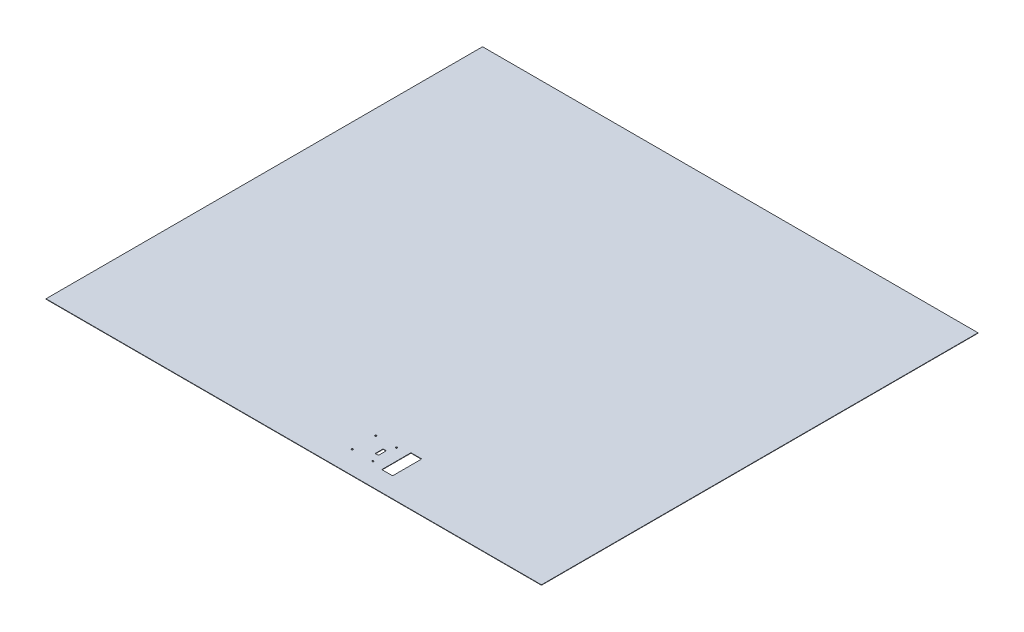
SolidWorks part; units mm, degrees
ref_plane "Front Plane" through (0, 0, 0) normal (0, 0, 1) x (1, 0, 0)
ref_plane "Top Plane" through (0, 0, 0) normal (0, 1, 0) x (1, 0, 0)
ref_plane "Right Plane" through (0, 0, 0) normal (1, 0, 0) x (0, 0, -1)
sketch "Sketch1" plane through (0, 0, 0) normal (0, 1, 0) x (1, 0, 0)
  line L1 (612.6065, -310.951) -> (-627.8935, -310.951)
  line L2 (612.6065, -310.951) -> (612.6065, 782.049)
  line L3 (612.6065, 782.049) -> (-627.8935, 782.049)
  line L4 (-627.8935, -310.951) -> (-627.8935, 782.049)
  dimension "D1" = 1093
  dimension "D2" = 1240.5
extrude "Boss-Extrude1" add sketch "Sketch1" along normal blind 1
sketch "Sketch2" plane through (0, 1, 0) normal (0, 1, 0) x (1, 0, 0)
  line L0 (-627.8935, -310.951) -> (612.6065, -310.951) construction
  line L1 (162.8565, -187.951) -> (189.8565, -187.951)
  line L2 (162.8565, -187.951) -> (162.8565, -260.951)
  line L3 (162.8565, -260.951) -> (189.8565, -260.951)
  line L4 (189.8565, -187.951) -> (189.8565, -260.951)
  line L5 (612.6065, -310.951) -> (612.6065, 782.049) construction
  line L6 (-627.8935, 782.049) -> (-627.8935, -310.951) construction
  point P6 (176.3565, -260.951)
  point P9 (189.8565, -224.451)
  dimension "D1" = 27
  dimension "D2" = 73
  dimension "D3" = 50
  dimension "D4" = 422.75
  dimension "D5" = 790.75
extrude "Cut-Extrude1" cut sketch "Sketch2" against normal blind 1
sketch "Sketch3" plane through (0, 1, 0) normal (0, 1, 0) x (1, 0, 0)
  line L0 (189.8565, -187.951) -> (162.8565, -187.951) construction
  line L1 (162.8565, -260.951) -> (189.8565, -260.951) construction
  line L2 (162.8565, -187.951) -> (162.8565, -260.951) construction
  circle A0 centre (133.6565, -194.951) radius 2
  circle A1 centre (133.6565, -253.951) radius 2
  circle A2 centre (81.9765, -194.951) radius 2
  circle A3 centre (81.9765, -253.951) radius 2
  dimension "D1" = 4
  dimension "D2" = 4
  dimension "D3" = 4
  dimension "D4" = 4
  dimension "D5" = 7
  dimension "D6" = 7
  dimension "D7" = 29.2
  dimension "D8" = 29.2
  dimension "D9" = 7
  dimension "D10" = 7
  dimension "D11" = 51.68
  dimension "D12" = 51.68
extrude "Cut-Extrude2" cut sketch "Sketch3" against normal through all
sketch "Sketch4" plane through (0, 1, 0) normal (0, 1, 0) x (1, 0, 0)
  line L1 (127.7565, -214.451) -> (119.7565, -214.451)
  line L2 (127.7565, -214.451) -> (127.7565, -234.451)
  line L3 (127.7565, -234.451) -> (119.7565, -234.451)
  line L4 (119.7565, -214.451) -> (119.7565, -234.451)
  circle A0 centre (133.6565, -194.951) radius 2 construction
  circle A1 centre (133.6565, -253.951) radius 2 construction
  dimension "D1" = 20
  dimension "D2" = 8
  dimension "D3" = 19.5
  dimension "D4" = 19.5
  dimension "D5" = 5.9
extrude "Cut-Extrude3" cut sketch "Sketch4" against normal blind 1
fillet "Fillet1" radius 2 4 edges at (119.7565, 0.5, 214.451) (119.7565, 0.5, 234.451) (127.7565, 0.5, 234.451) (127.7565, 0.5, 214.451)
